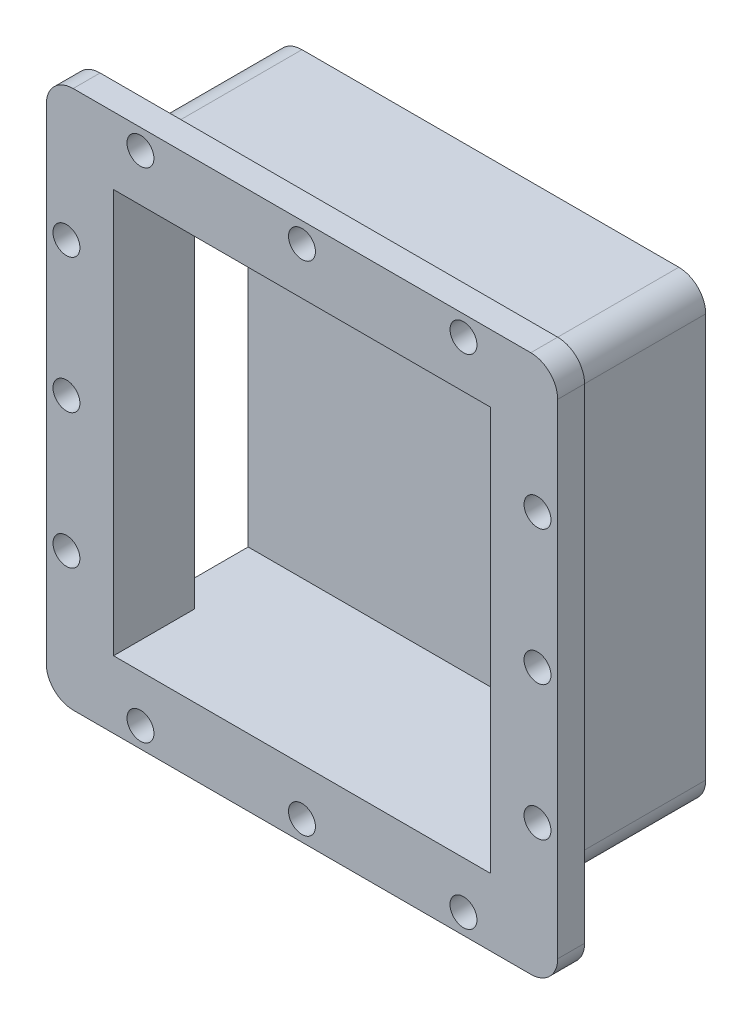
SolidWorks part; units mm, degrees
ref_plane "前视基准面" through (0, 0, 0) normal (0, 0, 1) x (1, 0, 0)
ref_plane "上视基准面" through (0, 0, 0) normal (0, 1, 0) x (1, 0, 0)
ref_plane "右视基准面" through (0, 0, 0) normal (1, 0, 0) x (0, 0, -1)
sketch "草图1" plane through (0, 0, 0) normal (0, 0, 1) x (1, 0, 0)
  line L1 (-70, -85) -> (70, -85)
  line L2 (-80, -75) -> (-80, 75)
  line L3 (-70, 85) -> (70, 85)
  line L4 (80, -75) -> (80, 75)
  line L5 (-80, -85) -> (80, 85) construction
  line L6 (-80, 85) -> (80, -85) construction
  arc A0 (70, -85) -> (80, -75) centre (70, -75) ccw
  arc A1 (-70, -85) -> (-80, -75) centre (-70, -75) cw
  arc A2 (-80, 75) -> (-70, 85) centre (-70, 75) cw
  arc A3 (70, 85) -> (80, 75) centre (70, 75) cw
  point P0 (0, 0)
  dimension "D3" = 10
  dimension "D1" = 170
  dimension "D2" = 160
extrude "凸台-拉伸1" add sketch "草图1" along normal blind 60
sketch "草图5" plane through (-80, 0, 0) normal (-1, 0, 0) x (0, 0, 1)
  line L0 (0, 0) -> (40, 0) construction
  line L1 (10, -75) -> (10, 75)
  line L3 (10, 75) -> (40, 75)
  line L4 (40, 75) -> (40, -75)
  line L5 (10, -75) -> (40, -75)
  line L6 (0, 75) -> (0, -75) construction
  point P4 (0, 0)
  point P8 (0, 0)
  dimension "D1" = 150
  dimension "D2" = 30
  dimension "D3" = 10
extrude "切除-拉伸2" cut sketch "草图5" against normal blind 150 and the other way through all
sketch "草图7" plane through (0, 0, 60) normal (0, 0, 1) x (1, 0, 0)
  line L0 (0, 0) -> (0, 92.5) construction
  line L1 (-85, -100) -> (85, -100)
  line L2 (-95, -90) -> (-95, 90)
  line L3 (-85, 100) -> (85, 100)
  line L4 (95, -90) -> (95, 90)
  line L5 (-95, -100) -> (95, 100) construction
  line L6 (-95, 100) -> (95, -100) construction
  line L11 (-74.6232, -78.5508) -> (74.6232, 78.5508) construction
  line L12 (-74.6232, 78.5508) -> (74.6232, -78.5508) construction
  line L13 (0, 0) -> (87.5, 0) construction
  line L15 (-87.5, -92.5) -> (87.5, -92.5) construction
  line L16 (-87.5, -92.5) -> (-87.5, 92.5) construction
  line L17 (-87.5, 92.5) -> (87.5, 92.5) construction
  line L18 (87.5, -92.5) -> (87.5, 92.5) construction
  line L19 (-87.5, -92.5) -> (87.5, 92.5) construction
  line L20 (-87.5, 92.5) -> (87.5, -92.5) construction
  arc A0 (85, -100) -> (95, -90) centre (85, -90) ccw
  arc A1 (-85, -100) -> (-95, -90) centre (-85, -90) cw
  arc A2 (85, 100) -> (95, 90) centre (85, 90) cw
  arc A3 (-95, 90) -> (-85, 100) centre (-85, 90) cw
  circle A4 centre (0, 92.5) radius 5
  circle A5 centre (-60, 92.5) radius 5
  circle A6 centre (-87.5, 0) radius 5
  circle A7 centre (-87.5, 50) radius 5
  circle A8 centre (87.5, 0) radius 5
  circle A9 centre (87.5, 50) radius 5
  circle A10 centre (60, 92.5) radius 5
  circle A11 centre (-87.5, -50) radius 5
  circle A12 centre (87.5, -50) radius 5
  circle A13 centre (60, -92.5) radius 5
  circle A14 centre (0, -92.5) radius 5
  circle A15 centre (-60, -92.5) radius 5
  point P0 (0, 0)
  point P18 (0, 0)
  point P28 (0, 0)
  point P50 (-59.9304, 94.8897)
  point P51 (0, 0)
  dimension "D3" = 10
  dimension "D6" = 10
  dimension "D7" = 10
  dimension "D8" = 60
  dimension "D9" = 10
  dimension "D10" = 10
  dimension "D11" = 50
  dimension "D1" = 200
  dimension "D2" = 190
  dimension "D4" = 175
  dimension "D5" = 185
extrude "凸台-拉伸2" add sketch "草图7" along normal blind 10
sketch "草图8" plane through (0, 0, 70) normal (0, 0, 1) x (1, 0, 0)
  line L1 (-70, -75) -> (70, -75)
  line L2 (-70, -75) -> (-70, 75)
  line L3 (-70, 75) -> (70, 75)
  line L4 (70, -75) -> (70, 75)
  line L5 (-70, -75) -> (70, 75) construction
  line L6 (-70, 75) -> (70, -75) construction
  point P0 (0, 0)
  dimension "D1" = 150
  dimension "D2" = 140
extrude "切除-拉伸4" cut sketch "草图8" against normal blind 40
